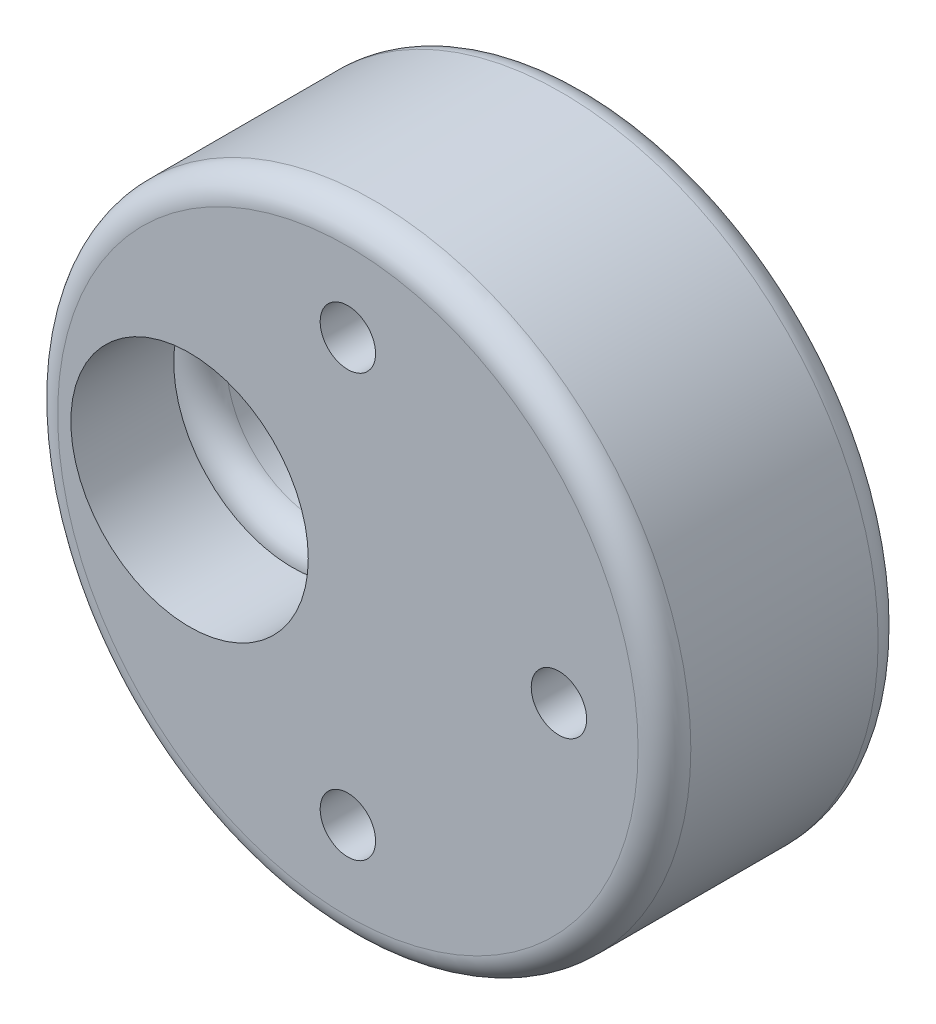
SolidWorks part; units mm, degrees
ref_plane "Front Plane" through (0, 0, 0) normal (0, 0, 1) x (1, 0, 0)
ref_plane "Top Plane" through (0, 0, 0) normal (0, 1, 0) x (1, 0, 0)
ref_plane "Right Plane" through (0, 0, 0) normal (1, 0, 0) x (0, 0, -1)
sketch "Sketch1" plane through (0, 0, 0) normal (0, 0, 1) x (1, 0, 0)
  circle A0 centre (0, 0) radius 12
  circle A1 centre (0, 8) radius 1.05
  circle A2 centre (8, 0) radius 1.05
  circle A3 centre (0, -8) radius 1.05
  circle A4 centre (-8, 0) radius 1.05 [skipped]
  dimension "D1" = 24
  dimension "D4" = 2.1
  dimension "D3" = 8
  dimension "D2" = 3
extrude "Boss-Extrude1" add sketch "Sketch1" along normal blind 9.1
hole_wizard "Hole2" positions "Sketch7" profile "Sketch6" legacy
sketch "Sketch7" plane through (0, 0, 9.1) normal (0, 0, 1) x (1, 0, 0)
  line L0 (0, 0) -> (-14.5014, 0) construction
  point P0 (-6, 0)
  dimension "D1" = 6
sketch "Sketch6" plane through (-6, 0, 9.1) normal (1, 0, 0) x (0, -1, 0)
  line L0 (0, 0) -> (0, 12)
  line L1 (0, 12) -> (3.5, 12)
  line L2 (3.5, 12) -> (3.5, 3.9)
  line L3 (3.5, 3.9) -> (4.5, 3.9)
  line L4 (4.5, 3.9) -> (4.5, 0)
  line L5 (4.5, 0) -> (0, 0)
  line L6 (0, 110) -> (0, -10) construction
  dimension "Diameter" = 7
  dimension "Depth" = 12
  dimension "C-Bore Diameter" = 9
  dimension "C-Bore Depth" = 3.9
sketch "Sketch8" plane through (0, 0, 0) normal (0, 0, -1) x (-1, 0, 0)
  circle A0 centre (0, 8) radius 2.15
  circle A1 centre (0, -8) radius 2.15
  circle A2 centre (-8, 0) radius 2.15
  dimension "D1" = 4.3
extrude "Cut-Extrude1" cut sketch "Sketch8" against normal blind 6.2
fillet "Fillet1" radius 1 4 edges at (12, 0, 0) (-2.5, 0, 0) (12, 0, 9.1) (-2.5, 0, 5.2)
